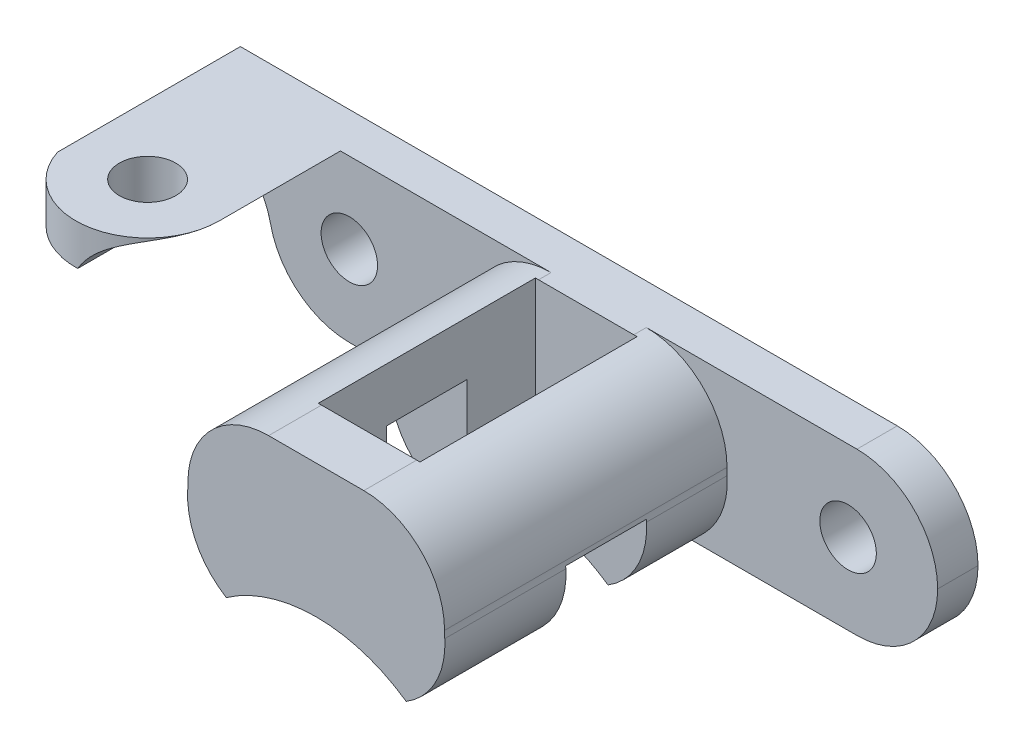
SolidWorks part; units mm, degrees
ref_plane "Front Plane" through (0, 0, 0) normal (0, 0, 1) x (1, 0, 0)
ref_plane "Top Plane" through (0, 0, 0) normal (0, 1, 0) x (1, 0, 0)
ref_plane "Right Plane" through (0, 0, 0) normal (1, 0, 0) x (0, 0, -1)
sketch "Sketch2" plane through (0, 0, 0) normal (0, 0, 1) x (1, 0, 0)
  line L0 (-15.45, 0) -> (15.45, 0) construction
  line L1 (-21, 5) -> (21, 5)
  line L2 (-21, 5) -> (-21, -5)
  line L3 (-21, -5) -> (21, -5)
  line L4 (21, 5) -> (21, -5)
  line L5 (0, 0) -> (0, 5) construction
  line L6 (15.45, 0) -> (21, 0) construction
  line L7 (0, 0) -> (0, -13) construction
  circle A0 centre (-15.45, 0) radius 2.8
  circle A1 centre (15.45, 0) radius 2.8
  circle A2 centre (0, -13) radius 9.75
  dimension "D1" = 5.6
  dimension "D5" = 19.5
  dimension "D2" = 30.9
  dimension "D3" = 10
  dimension "D4" = 42
  dimension "D6" = 13
extrude "Boss-Extrude1" add sketch "Sketch2" along normal blind 20 contours A2 L3 L4 L1 L2 A1 A0 region at (0, 0.1593, 0)
sketch "Sketch3" plane through (0, 5, 0) normal (0, 1, 0) x (1, 0, 0)
  line L0 (0, 0) -> (0, -3.275) construction
  line L1 (-3.15, -3.275) -> (3.15, -3.275)
  line L2 (-3.15, -3.275) -> (-3.15, -16.725)
  line L3 (-3.15, -16.725) -> (3.15, -16.725)
  line L4 (3.15, -3.275) -> (3.15, -16.725)
  line L6 (3.15, -10) -> (21, -10) construction
  line L7 (21, -20) -> (21, 0) construction
  dimension "D1" = 13.45
  dimension "D2" = 6.3
extrude "Cut-Extrude1" cut sketch "Sketch3" against normal through all
sketch "Sketch4" plane through (0, 0, 20) normal (0, 0, 1) x (1, 0, 0)
  circle A0 centre (-15.45, 0) radius 7.5
  circle A1 centre (15.45, 0) radius 7.5
  dimension "D1" = 15
extrude "Cut-Extrude2" cut sketch "Sketch4" against normal offset from surface (17.5 mm away) 2.5 up to face at (0, -1.375, 0)
sketch "Sketch5" plane through (0, -5, 0) normal (0, -1, 0) x (1, 0, 0)
  line L0 (-9.8598, 20) -> (-9.8598, 2.5) construction
  line L1 (-9.8598, 12.5) -> (9.8598, 12.5)
  line L2 (-9.8598, 12.5) -> (-9.8598, 7.5)
  line L3 (-9.8598, 7.5) -> (9.8598, 7.5)
  line L4 (9.8598, 12.5) -> (9.8598, 7.5)
  line L5 (9.8598, 2.5) -> (9.8598, 20) construction
  line L6 (-9.8598, 10) -> (-3.15, 10) construction
  line L7 (-3.15, 16.725) -> (-3.15, 3.275) construction
  dimension "D1" = 5
ref_plane "Plane1" through (0, 0, 10) normal (0, 0, 1) x (1, 0, 0)
sketch "Sketch6" plane through (0, 0, 10) normal (0, 0, 1) x (1, 0, 0)
  circle A0 centre (0, -13) radius 15
  arc A1 (5.5734, -5) -> (-5.5734, -5) centre (0, -13) ccw construction
  dimension "D1" = 30
extrude "Cut-Extrude3" cut sketch "Sketch6" against normal blind 2.5 and the other way blind 2.5
fillet "Fillet1" radius 5 4 edges at (21, -5, 1.25) (21, 5, 1.25) (-21, -5, 1.25) (-21, 5, 1.25)
fillet "Fillet2" radius 5 6 edges at (9.8598, -5, 16.25) (9.8598, -5, 5) (9.8598, 5, 11.25) (-9.8598, -5, 5) (-9.8598, -5, 16.25) (-9.8598, 5, 11.25)
sketch "Sketch7" plane through (0, 0, 0) normal (0, 0, -1) x (-1, 0, 0)
  line L0 (16, 5) -> (31.7969, 5)
  line L1 (31.7969, 5) -> (31.7969, -5)
  line L2 (31.7969, -5) -> (16, -5)
  line L3 (21, 0) -> (31.7969, 0) construction
  arc A0 (16, 5) -> (21, 0) centre (16, 0) cw
  arc A1 (21, 0) -> (16, -5) centre (16, 0) cw
extrude "Boss-Extrude2" add sketch "Sketch7" against normal blind 20
sketch "Sketch8" plane through (0, -5, 0) normal (0, -1, 0) x (1, 0, 0)
  line L0 (-20.45, 10) -> (-3.15, 10) construction
  line L1 (-3.15, 7.5) -> (-3.15, 12.5) construction
  circle A0 centre (-20.45, 10) radius 1.75
  dimension "D1" = 3.5
  dimension "D2" = 17.3
extrude "Cut-Extrude4" cut sketch "Sketch8" against normal through all
sketch "Sketch9" plane through (0, 0, 20) normal (0, 0, 1) x (1, 0, 0)
  line L0 (-31.7969, 5) -> (-31.7969, -5)
  line L1 (-31.7969, -5) -> (-24.7, -5)
  line L3 (-24.7, -5) -> (-24.7, 5)
  line L4 (-31.7969, 5) -> (-16, 5) construction
  line L5 (-24.7, 5) -> (-31.7969, 5)
  dimension "D1" = 2.5
extrude "Cut-Extrude5" cut sketch "Sketch9" against normal blind 20
sketch "Sketch10" plane through (0, 0, 2.5) normal (0, 0, 1) x (1, 0, 0)
  line L0 (-24.7, 5) -> (-16, 5) construction
  line L1 (-24.7, -5) -> (-16, -5)
  line L2 (-24.7, -5) -> (-24.7, 2.5)
  line L3 (-24.7, 2.5) -> (-16, 2.5)
  line L4 (-16, -5) -> (-16, 2.5)
  arc A0 (-16, 5) -> (-16, -5) centre (-16, 0) ccw construction
  arc A1 (-16, 5) -> (-16, -5) centre (-16, 0) ccw construction
  dimension "D1" = 2.5
extrude "Cut-Extrude6" cut sketch "Sketch10" along normal through all
sketch "Sketch11" plane through (0, 2.5, 0) normal (0, -1, 0) x (1, 0, 0)
  line L1 (-24.7, 10) -> (-24.7, 20)
  line L2 (-24.7, 20) -> (-16, 20)
  line L3 (-16, 20) -> (-16, 10)
  line L4 (-16, 20) -> (-16, 2.5) construction
  line L5 (-24.7, 20) -> (-24.7, 2.5) construction
  circle A0 centre (-20.45, 10) radius 4.45
  line M2 (-20.3301, 20) -> (-24.7, 20)
  line M3 (-24.7, 20) -> (-24.7, 2.5)
  line M7 (-20.3301, 11.7459) -> (-20.3301, 20)
extrude "Cut-Extrude7" cut sketch "Sketch11" against normal through all contours A0 L3 L2 M7 | A0 M7 M2 M3 region at (-22.669, 2.5, 16.766) region at (-17.9891, 2.5, 16.6587)
fillet "Fillet4" radius 5 1 edges at (-22.5151, 2.5, 2.5)
sketch "Sketch12" plane through (0, 0, 2.5) normal (0, 0, 1) x (1, 0, 0)
  line L0 (-24.7, -5) -> (-5.5734, -5) construction
  line L1 (-24.7, -2.5) -> (-24.7, -5) construction
  line L2 (-15.45, -5) -> (-21.45, -5)
  circle A0 centre (-15.45, 0) radius 5
  circle A1 centre (-15.45, 0) radius 2.8 construction
  circle A2 centre (-24.7, -1.9542) radius 4.4542
  line M3 (-24.7, -2.5) -> (-24.7, -5)
  line M4 (-24.7, -5) -> (-5.5734, -5)
  arc M9 (-16, 5) -> (-20.3301, -2.5) centre (-16, 0) ccw
  line M16 (-20.3301, -2.5) -> (-24.7, -2.5)
extrude "Cut-Extrude9" cut sketch "Sketch12" against normal through all both and the other way through all contours A2 M9 M4 M3 M16 | A2 A0 M4 | A2 M9 M16 M3 M4 region at (-19.4413, -4.0891, 2.5) region at (-22.4773, -3.4211, 2.5) region at (-25.1828, -1.6355, 2.5)
sketch "Sketch13" plane through (0, 0, 0) normal (0, 0, 1) x (1, 0, 0)
  circle A0 centre (-15.45, 0) radius 2.8
  circle A1 centre (15.45, 0) radius 2.8
  circle A2 centre (15.45, 0) radius 2.8 construction
  circle A3 centre (-15.45, 0) radius 2.8 construction
  circle A4 centre (-15.45, 0) radius 1.75
  circle A5 centre (15.45, 0) radius 1.75
  dimension "D1" = 3.5
extrude "Boss-Extrude3" add sketch "Sketch13" along normal up to surface (2.5 mm away) up to face at (-12.5464, -0.0195, 2.5)
